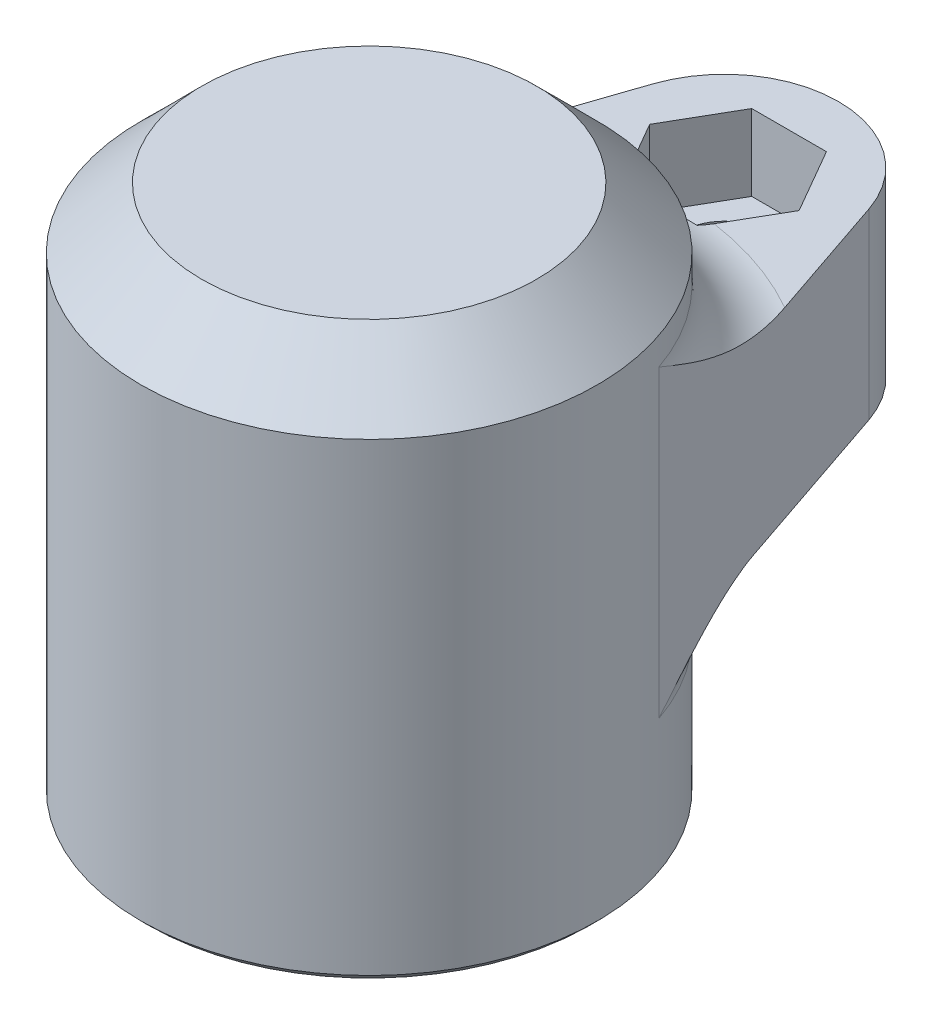
SolidWorks part; units mm, degrees
ref_plane "Front Plane" through (0, 0, 0) normal (0, 0, 1) x (1, 0, 0)
ref_plane "Top Plane" through (0, 0, 0) normal (0, 1, 0) x (1, 0, 0)
ref_plane "Right Plane" through (0, 0, 0) normal (1, 0, 0) x (0, 0, -1)
sketch "Sketch5" plane through (0, 0, 0) normal (0, 1, 0) x (1, 0, 0)
  circle A0 centre (0, 0) radius 15
  dimension "D1" = 30
extrude "Boss-Extrude3" add sketch "Sketch5" along normal blind 35
sketch "Sketch7" plane through (0, 0, 0) normal (1, 0, 0) x (0, 0, -1)
  line L0 (0, 0) -> (12, 0)
  line L1 (-15, 0) -> (15, 0) construction
  line L2 (12, 0) -> (12, 5)
  line L3 (12, 5) -> (5.5, 11.5)
  line L4 (5.5, 11.5) -> (5.5, 30)
  line L5 (5.5, 30) -> (0, 30)
  line L6 (0, 30) -> (0, 0)
  dimension "D1" = 5
  dimension "D2" = 12
  dimension "D3" = 45
  dimension "D4" = 30
  dimension "D5" = 5.5
revolve "Cut-Revolve1" cut sketch "Sketch7" angle 360 about L6
sketch "Sketch8" plane through (0, 35, 0) normal (0, 1, 0) x (1, 0, 0)
  line L0 (0, 0) -> (0, 23.3363) construction
  circle A0 centre (0, 23.3363) radius 7.5
  circle A1 centre (0, 23.3363) radius 2.75
  dimension "D1" = 5.5
  dimension "D2" = 15
extrude "Boss-Extrude4" add sketch "Sketch8" against normal blind 15 from offset 10.8 separate body offset against normal yes
chamfer "Chamfer1" distance 3 angle 45 1 edges at (0, 9.2, -15.8363)
sketch "Sketch9" plane through (0, 24.2, 0) normal (0, 1, 0) x (1, 0, 0)
  line L0 (7.1021, 25.7467) -> (14.2042, 4.8208)
  line L1 (-7.1021, 25.7467) -> (-14.2042, 4.8208)
  circle A0 centre (0, 0) radius 15 construction
  circle A1 centre (0, 23.3363) radius 7.5 construction
  arc A2 (14.2042, 4.8208) -> (-14.2042, 4.8208) centre (0, 0) ccw
  arc A3 (-7.1021, 25.7467) -> (7.1021, 25.7467) centre (0, 23.3363) ccw
extrude "Boss-Extrude5" add sketch "Sketch9" against normal blind 12
fillet "Fillet1" radius 5 1 edges at (0, 24.2, -15)
sketch "Sketch10" plane through (0, 24.2, 0) normal (0, 1, 0) x (1, 0, 0)
  line L0 (-16.5, 0) -> (16.5, 0) construction
  line L1 (4.9075, 23.3363) -> (2.4537, 27.5863)
  line L2 (2.4537, 27.5863) -> (-2.4537, 27.5863)
  line L3 (-2.4537, 27.5863) -> (-4.9075, 23.3363)
  line L4 (-4.9075, 23.3363) -> (-2.4537, 19.0863)
  line L5 (-2.4537, 19.0863) -> (2.4537, 19.0863)
  line L6 (2.4537, 19.0863) -> (4.9075, 23.3363)
  circle A0 centre (0, 23.3363) radius 4.25 construction
  dimension "D1" = 8.5
extrude "Cut-Extrude1" cut sketch "Sketch10" against normal blind 5 and the other way blind 12
chamfer "Chamfer2" distance 4 angle 45 1 edges at (0, 35, 15)
chamfer "Chamfer3" distance 0.5 angle 45 1 edges at (0, 0, 15)
fillet "Fillet2" radius 3 1 edges at (0, 12.2, -15)
